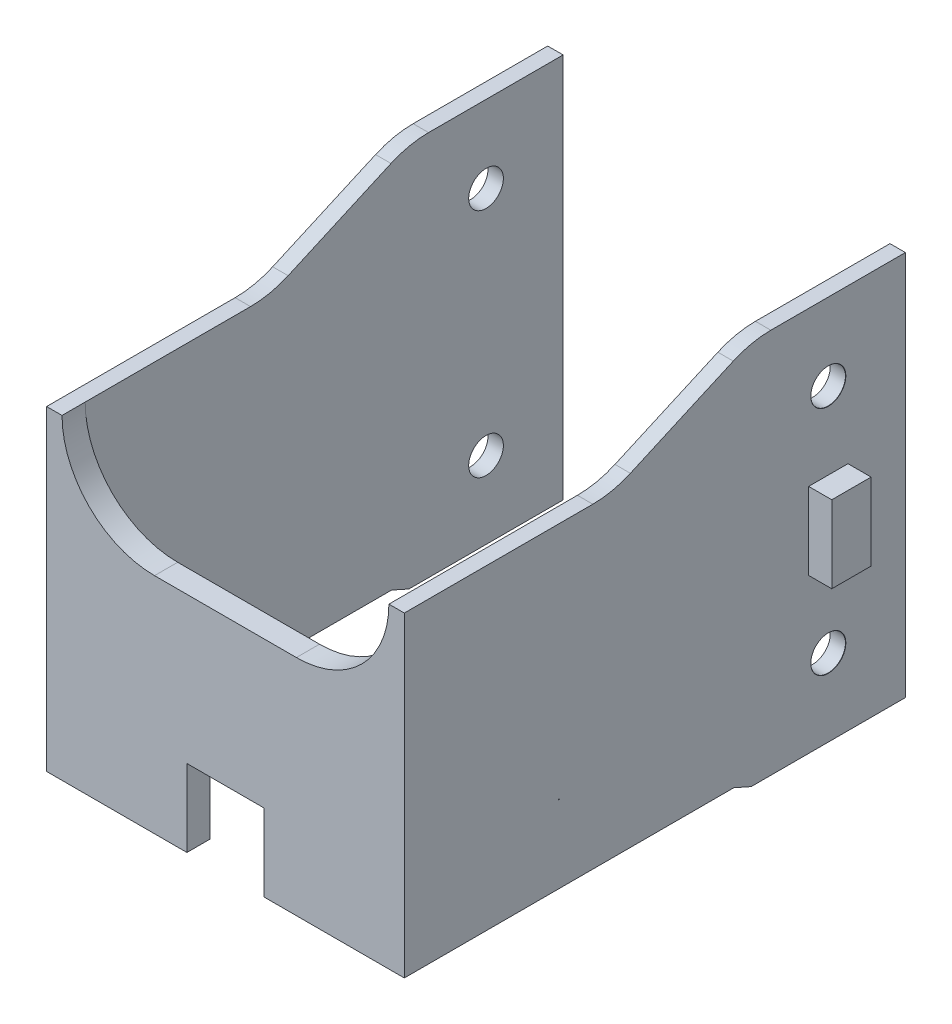
SolidWorks part; units mm, degrees
ref_plane "정면" through (0, 0, 0) normal (0, 0, 1) x (1, 0, 0)
ref_plane "윗면" through (0, 0, 0) normal (0, 1, 0) x (1, 0, 0)
ref_plane "우측면" through (0, 0, 0) normal (1, 0, 0) x (0, 0, -1)
sketch "스케치1" plane through (0, 0, 0) normal (0, 0, 1) x (1, 0, 0)
  line L1 (-23.2, 5) -> (-21.2, 5)
  line L2 (-23.2, 5) -> (-23.2, -5)
  line L3 (-23.2, -5) -> (-21.2, -5)
  line L4 (-21.2, 5) -> (-21.2, -5)
  line L5 (21.2, 5) -> (23.2, 5)
  line L6 (21.2, 5) -> (21.2, -5)
  line L7 (21.2, -5) -> (23.2, -5)
  line L8 (23.2, 5) -> (23.2, -5)
  dimension "D1" = 2
  dimension "D2" = 2
  dimension "D3" = 10
  dimension "D4" = 10
  dimension "D5" = 21.2
  dimension "D6" = 21.2
  dimension "D7" = 5
  dimension "D8" = 5
extrude "보스-돌출1" add sketch "스케치1" along normal blind 62
sketch "스케치2" plane through (0, 0, 62) normal (0, 0, 1) x (1, 0, 0)
  line L1 (-23.2, 5) -> (23.2, 5)
  line L2 (-23.2, 5) -> (-23.2, -5)
  line L3 (-23.2, -5) -> (23.2, -5)
  line L4 (23.2, 5) -> (23.2, -5)
extrude "보스-돌출2" add sketch "스케치2" along normal blind 3
sketch "스케치3" plane through (0, 5, 0) normal (0, 1, 0) x (1, 0, 0)
  line L0 (-21.2, -62) -> (-21.2, 0) construction
  line L1 (-23.2, 0) -> (-21.2, 0)
  line L2 (-23.2, 0) -> (-23.2, -20)
  line L3 (-23.2, -20) -> (-21.2, -20)
  line L4 (-21.2, 0) -> (-21.2, -20)
  line L5 (23.2, -65) -> (23.2, 0) construction
  line L6 (21.2, 0) -> (23.2, 0)
  line L7 (21.2, 0) -> (21.2, -20)
  line L8 (21.2, -20) -> (23.2, -20)
  line L9 (23.2, 0) -> (23.2, -20)
  dimension "D1" = 20
  dimension "D2" = 20
extrude "보스-돌출3" add sketch "스케치3" along normal blind 20
ref_plane "평면1" through (0, 0, 0) normal (0, 1, 0) x (1, 0, 0)
sketch "스케치4" plane through (21.2, 0, 0) normal (-1, 0, 0) x (0, 0, 1)
  line L0 (20, 25) -> (20, 5)
  line L1 (20, 5) -> (65, 5)
  line L2 (65, 5) -> (20, 25)
extrude "보스-돌출4" add sketch "스케치4" against normal blind 2
mirror "대칭 복사1" about plane through (0, 0, 0) normal (0, 1, 0) of "보스-돌출4", "보스-돌출3"
ref_plane "평면2" through (0, 0, 0) normal (-1, 0, 0) x (0, 0, 1)
mirror "대칭 복사3" about plane through (0, 0, 0) normal (-1, 0, 0) of "대칭 복사1"
sketch "스케치6" plane through (0, -5, 0) normal (0, -1, 0) x (1, 0, 0)
  line L0 (-23.2, 65) -> (-23.2, 44.6374)
  line L1 (-23.2, 65) -> (-23.2, 20) construction
  line L2 (-23.2, 65) -> (-21.2, 65) construction
  line L3 (-23.2, 44.6374) -> (-21.2, 44.6374)
  line L4 (-21.2, 65) -> (-21.2, 20) construction
  line L5 (-21.2, 44.6374) -> (-21.2, 62)
  line L6 (-21.2, 62) -> (21.2, 62) construction
  line L7 (-23.2, 65) -> (23.2, 65)
  line L8 (23.2, 65) -> (23.2, 45)
  line L9 (23.2, 45) -> (21.2, 45)
  line L10 (21.2, 45) -> (21.2, 62)
  line L11 (21.2, 62) -> (-21.2, 62)
  line L12 (21.2, 62) -> (21.2, 65) construction
  dimension "D1" = 0
  dimension "D2" = 2
  dimension "D3" = 0
  dimension "D4" = 20
extrude "보스-돌출5" add sketch "스케치6" along normal blind 9
hole_wizard "M4 여유 구멍1" positions "스케치7" profile "스케치9" hole size "M4" standard "KS" end condition through all
sketch "스케치7" plane through (23.2, 0, 0) normal (1, 0, 0) x (0, 0, -1)
  line L0 (0, -25) -> (0, 25) construction
  line L1 (-20, -25) -> (0, -25) construction
  line L2 (-20, 25) -> (0, 25) construction
  point P0 (-10, -15)
  point P2 (-10, 15)
  dimension "D1" = 10
  dimension "D2" = 10
  dimension "D3" = 10
  dimension "D4" = 10
sketch "스케치9" plane through (23.2, -15, 10) normal (0, 1, 0) x (0, 0, -1)
  line L0 (0, 0) -> (0, 46.4)
  line L1 (0, 46.4) -> (2.25, 46.4)
  line L2 (2.25, 46.4) -> (2.25, 0.025)
  line L3 (2.25, 0.025) -> (2.275, 0)
  line L5 (2.275, 0) -> (0, 0)
  line L6 (-2.25, 0.025) -> (-2.275, 0) construction
  line L11 (0, -6.35) -> (0, 107.95) construction
  dimension "관통 구멍 지름" = 4.5
  dimension "관통 구멍 깊이" = 46.4
  dimension "표면 카운터싱크 지름" = 4.55
  dimension "표면 카운터싱크 각도" = 90
sketch "스케치10" plane through (23.2, 0, 0) normal (1, 0, 0) x (0, 0, -1)
  line L0 (0, -25) -> (0, 25) construction
  line L1 (-12.55, 5) -> (-7.45, 5)
  line L2 (-12.55, 5) -> (-12.55, -5)
  line L3 (-12.55, -5) -> (-7.45, -5)
  line L4 (-7.45, 5) -> (-7.45, -5)
  line L5 (-12.55, 5) -> (-7.45, -5) construction
  line L6 (-12.55, -5) -> (-7.45, 5) construction
  line L7 (-20, 25) -> (0, 25) construction
  point P0 (-10, 0)
  dimension "D1" = 5.1
  dimension "D2" = 10
  dimension "D3" = 10
  dimension "D4" = 25
extrude "보스-돌출6" add sketch "스케치10" along normal blind 3
mirror "대칭 복사4" about plane through (0, 0, 0) normal (-1, 0, 0) of "보스-돌출6"
sketch "스케치11" plane through (0, -14, 0) normal (0, -1, 0) x (1, 0, 0)
  line L0 (-23.2, 15) -> (-21.2, 15)
  line L1 (-23.2, 44.75) -> (-23.2, 20) construction
  line L2 (-21.2, 44.75) -> (-21.2, 20) construction
  line L3 (-21.2, 15) -> (-21.2, 62)
  line L4 (-21.2, 44.75) -> (-21.2, 62) construction
  line L5 (-21.2, 62) -> (21.2, 62)
  line L6 (21.2, 62) -> (21.2, 15)
  line L7 (21.2, 45) -> (21.2, 20) construction
  line L8 (21.2, 15) -> (23.2, 15)
  line L9 (23.2, 45) -> (23.2, 20) construction
  line L10 (23.2, 15) -> (23.2, 65)
  line L11 (23.2, 45) -> (23.2, 65) construction
  line L12 (23.2, 65) -> (-23.2, 65)
  line L13 (-23.2, 65) -> (-23.2, 15)
  point P21 (-23.2, 65)
  point P23 (-23.2, 38.1292)
  dimension "D1" = 50
  dimension "D2" = 50
extrude "보스-돌출7" add sketch "스케치11" along normal blind 10
sketch "스케치12" plane through (0, 0, 65) normal (0, 0, 1) x (1, 0, 0)
  line L0 (-23.2, 5) -> (-23.2, 25) construction
  line L1 (-23.2, 17) -> (-21.2, 17)
  line L2 (-23.2, 17) -> (-23.2, -5)
  line L3 (-23.2, -5) -> (-21.2, -5)
  line L4 (-21.2, 17) -> (-21.2, -5)
  line L5 (-21.2, 5) -> (-21.2, 25) construction
  line L6 (0, 27.5) -> (0, -27.5) construction
  line L7 (21.2, 17) -> (21.2, -5)
  line L8 (23.2, -5) -> (21.2, -5)
  line L9 (23.2, 17) -> (23.2, -5)
  line L10 (23.2, 17) -> (21.2, 17)
  line L11 (21.2, 5) -> (-21.2, 5) construction
  dimension "D1" = 22
  dimension "D2" = 10
extrude "보스-돌출8" add sketch "스케치12" against normal up to next
sketch "스케치13" plane through (0, 0, 65) normal (0, 0, 1) x (1, 0, 0)
  line L0 (0, 27.5) -> (0, -27.5) construction
  line L1 (-5, -14) -> (5, -14)
  line L2 (-5, -14) -> (-5, -24)
  line L3 (-5, -24) -> (5, -24)
  line L4 (5, -14) -> (5, -24)
  line L5 (-5, -14) -> (5, -24) construction
  line L6 (-5, -24) -> (5, -14) construction
  line L7 (23.2, -24) -> (-23.2, -24) construction
  point P0 (0, -19)
  dimension "D1" = 10
  dimension "D2" = 10
extrude "컷-돌출1" cut sketch "스케치13" against normal blind 10
fillet "필렛1" radius 12 2 edges at (21.2, 5, 63.5) (-21.2, 5, 63.5)
fillet "필렛2" radius 12 4 edges at (22.2, 25, 20) (22.2, 17, 38) (-22.2, 17, 38) (-22.2, 25, 20)
